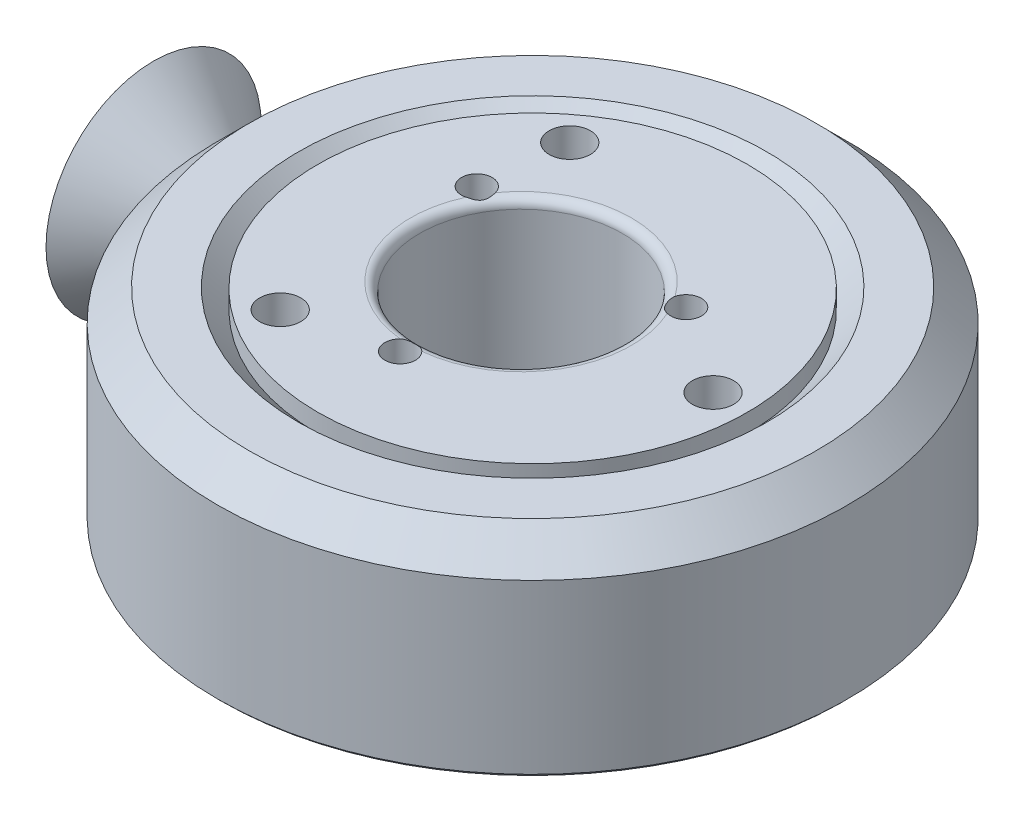
SolidWorks part; units mm, degrees
material "AISI 1020 Steel, Cold Rolled"
ref_plane "Front Plane" through (0, 0, 0) normal (0, 0, 1) x (1, 0, 0)
ref_plane "Top Plane" through (0, 0, 0) normal (0, 1, 0) x (1, 0, 0)
ref_plane "Right Plane" through (0, 0, 0) normal (1, 0, 0) x (0, 0, -1)
other "Center of Mass"
sketch "Sketch1" plane through (0, 0, 0) normal (0, 1, 0) x (1, 0, 0)
  circle A0 centre (0, 0) radius 34.925
  circle A1 centre (0, 0) radius 23.8125
  dimension "D1" = 69.85
  dimension "D2" = 47.625
extrude "Boss-Extrude1" add sketch "Sketch1" along normal mid plane 22.479
chamfer "Chamfer1" distance 2.159 angle 45 2 edges at (0, -11.2395, 23.8125) (0, 11.2395, 23.8125)
chamfer "Chamfer2" distance 3.4798 angle 45 1 edges at (0, 11.2395, 34.925)
chamfer "Chamfer3" distance 0.381 angle 45 1 edges at (0, -11.2395, 34.925)
sketch "Sketch2" plane through (0, 0, 0) normal (0, 1, 0) x (1, 0, 0)
  line L0 (-42.037, 11.9126) -> (-42.037, 0)
  line L1 (-42.037, 0) -> (-17.1196, 0)
  line L2 (-17.1196, 0) -> (-17.1196, 5.3693)
  line L3 (-17.1196, 5.3693) -> (-34.5098, 5.3693)
  line L4 (-34.5098, 5.3693) -> (-42.037, 11.9126)
  circle A0 centre (0, 0) radius 34.925 construction
  point P7 (34.925, 0)
  dimension "D1" = 24.9174
  dimension "D2" = 76.962
  dimension "D3" = 41
  dimension "D4" = 11.9126
revolve "Revolve1" add sketch "Sketch2" angle 360 about L1
other "Center of Mass Reference Point1"
chamfer "Chamfer4" distance 1.27 angle 45 1 edges at (-17.1196, 0, 5.3693)
sketch "Sketch3" plane through (0, 0, 0) normal (0, 1, 0) x (1, 0, 0)
  circle A0 centre (0, 0) radius 23.8125
  dimension "D1" = 47.625
extrude "Boss-Extrude2" add sketch "Sketch3" along normal mid plane 22.225 separate body
sketch "Sketch4" plane through (0, 11.1125, 0) normal (0, 1, 0) x (1, 0, 0)
  circle A0 centre (-1.2893, 0) radius 11.25
  dimension "D1" = 22.5
  dimension "D2" = 1.2893
extrude "Cut-Extrude1" cut sketch "Sketch4" against normal through all both and the other way through all
ref_axis "Axis1" through (-1.2893, -11.1125, 0) along (0, 1, 0)
sketch "Sketch6" plane through (-42.037, 0, 0) normal (-1, 0, 0) x (0, 0, 1)
  line L1 (-4.6194, 0) -> (-2.3097, -4.0005)
  line L2 (-2.3097, -4.0005) -> (2.3097, -4.0005)
  line L3 (2.3097, -4.0005) -> (4.6194, 0)
  line L4 (4.6194, 0) -> (2.3097, 4.0005)
  line L5 (2.3097, 4.0005) -> (-2.3097, 4.0005)
  line L6 (-2.3097, 4.0005) -> (-4.6194, 0)
  circle A0 centre (0, 0) radius 4.0005 construction
  dimension "D1" = 8.001
extrude "Cut-Extrude3" cut sketch "Sketch6" against normal blind 6.35
sketch "Sketch9" plane through (0, 0, 0) normal (0, 0, 1) x (1, 0, 0)
  line L0 (-23.8125, 6.604) -> (-15.8125, 6.604)
  line L1 (-15.8125, 6.604) -> (-15.8125, 0)
  line L2 (-15.8125, 0) -> (-23.8125, 0)
  line L3 (-23.8125, 0) -> (-23.8125, 6.604)
  line L4 (-23.8125, 11.1125) -> (-23.8125, -11.1125) construction
  dimension "D1" = 6.604
  dimension "D2" = 8
revolve "Cut-Revolve1" cut sketch "Sketch9" angle 360 about L2
sketch "Sketch12" plane through (0, -11.1125, 0) normal (0, -1, 0) x (1, 0, 0)
  circle A0 centre (-1.2893, 0) radius 11.25 construction
  circle A1 centre (-1.2893, 0) radius 11.25
  circle A2 centre (0, 0) radius 27.8125
  circle A5 centre (0, 0) radius 23.8125 construction
  dimension "D1" = 4
extrude "Boss-Extrude5" add sketch "Sketch12" along normal blind 2
sketch "Sketch13" plane through (0, -13.1125, 0) normal (0, -1, 0) x (1, 0, 0)
  circle A0 centre (-1.2893, 0) radius 11.25 construction
  circle A1 centre (-1.2893, 0) radius 11.25
  circle A2 centre (-1.2893, 0) radius 15.25
  dimension "D1" = 4
extrude "Boss-Extrude6" add sketch "Sketch13" along normal blind 7
sketch "Sketch14" plane through (0, -20.1125, 0) normal (0, -1, 0) x (1, 0, 0)
  circle A0 centre (-1.2893, 0) radius 11.25 construction
  circle A1 centre (-1.2893, 0) radius 11.25
  circle A2 centre (-1.2893, 0) radius 17.25
  circle A3 centre (-1.2893, 0) radius 15.25 construction
  dimension "D1" = 2
extrude "Boss-Extrude7" add sketch "Sketch14" along normal blind 2
sketch "Sketch15" plane through (0, -13.1125, 0) normal (0, -1, 0) x (1, 0, 0)
  line L0 (-11.9339, 16.0493) -> (0, 0) construction
  line L1 (0, 0) -> (-11.9339, -16.0493) construction
  line L2 (0, 0) -> (20, 0) construction
  line L3 (-11.9339, 16.0493) -> (-1.2893, 16.0493) construction
  line L4 (-1.2893, 16.0493) -> (9.3554, 16.0493) construction
  line L5 (9.3554, 16.0493) -> (20, 16.0493) construction
  line L6 (20, 16.0493) -> (20, 0) construction
  circle A0 centre (-11.9339, 16.0493) radius 2.286
  circle A1 centre (20, 0) radius 2.286
  circle A2 centre (-11.9339, -16.0493) radius 2.286
  dimension "D1" = 4.572
  dimension "D2" = 20
extrude "Cut-Extrude5" cut sketch "Sketch15" against normal through all
sketch "Sketch16" plane through (0, -22.1125, 0) normal (0, -1, 0) x (1, 0, 0)
  line L0 (10.3154, -6.7) -> (-1.2893, 0) construction
  line L1 (-1.2893, 0) -> (-12.894, -6.7) construction
  line L2 (-1.2893, 0) -> (-1.2893, 13.4) construction
  circle A0 centre (-12.894, -6.7) radius 1.7
  circle A1 centre (-1.2893, 13.4) radius 1.7
  circle A2 centre (10.3154, -6.7) radius 1.7
  circle A3 centre (-1.2893, 0) radius 11.25 construction
  dimension "D1" = 120
  dimension "D3" = 3.4
  dimension "D2" = 120
  dimension "D4" = 13.4
extrude "Cut-Extrude6" cut sketch "Sketch16" against normal through all
sketch "Sketch17" plane through (0, 0, 0) normal (0, 0, 1) x (1, 0, 0)
  line L1 (-12.5393, -16.1125) -> (-12.5393, -8.2605)
  line L2 (-12.5393, -16.1125) -> (-11.1251, -14.6983)
  line L3 (-11.1251, -14.6983) -> (-11.1251, -9.6747)
  line L4 (-11.1251, -9.6747) -> (-12.5393, -8.2605)
  line L6 (-12.5393, -22.1125) -> (9.9607, -22.1125) construction
  line L7 (-12.5393, 11.1125) -> (-12.5393, -22.1125) construction
  line L8 (31.4452, 11.2395) -> (-31.4452, 11.2395) construction
  dimension "D1" = 2
  dimension "D2" = 45
  dimension "D3" = 6
  dimension "D4" = 19.5
revolve "Revolve2" add sketch "Sketch17" angle 360 about axis through (-1.2893, -11.1125, 0) along (0, 1, 0)
chamfer "Chamfer5" distance 2 angle 45 6 edges at (-12.894, -22.1125, -8.4) (-11.9339, -13.1125, 13.7633) (20, -13.1125, -2.286) (-11.9339, -13.1125, -18.3353) (10.3154, -22.1125, -8.4) (-1.2893, -22.1125, 11.7)
fillet "Fillet1" radius 1 4 edges at (-1.2893, 11.1125, 11.25) (-1.2893, -22.1125, -11.25) (8.4535, -22.1125, 5.625) (-11.0321, -22.1125, 5.625)
ref_plane "Plane1" through (0, -13.1125, 0) normal (0, -1, 0) x (-1, 0, 0)
split "Split1" trim tools "Plane1" bodies to split 130 resulting bodies 131 132
